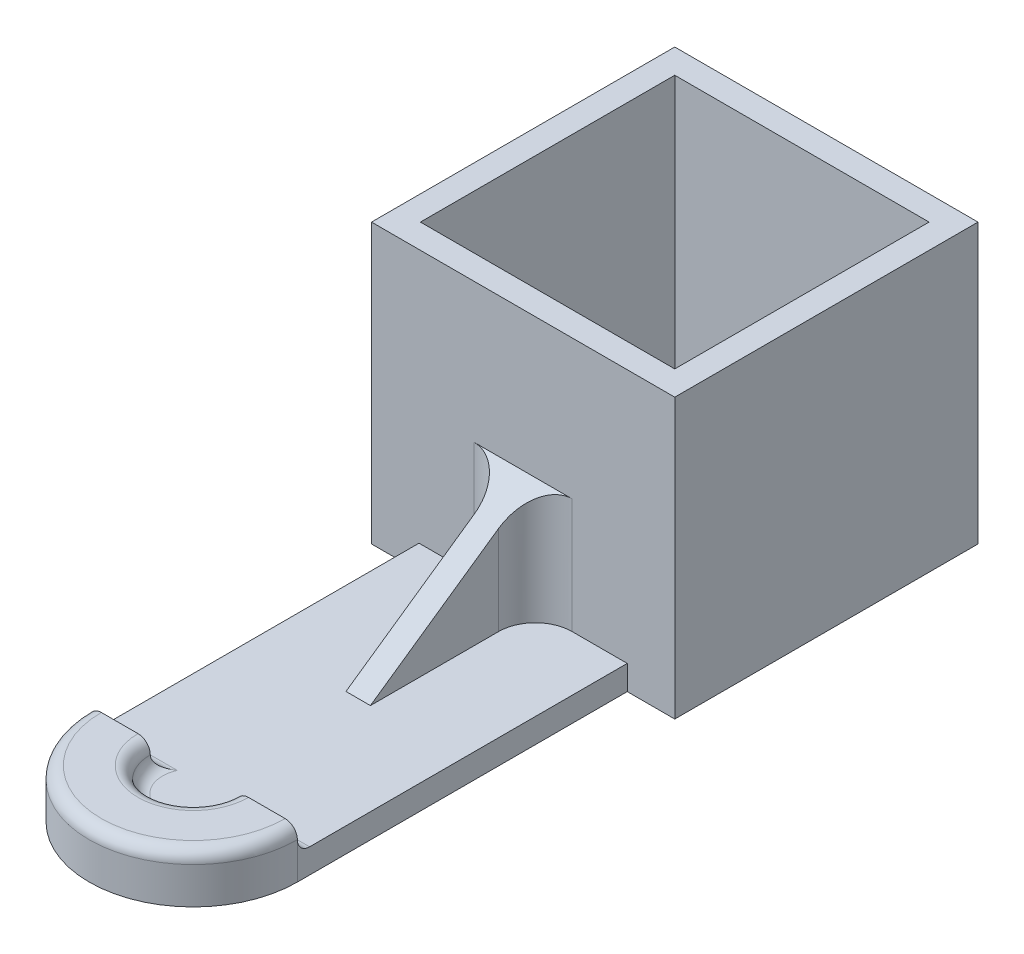
SolidWorks part; units mm, degrees
ref_plane "Front Plane" through (0, 0, 0) normal (0, 0, 1) x (1, 0, 0)
ref_plane "Top Plane" through (0, 0, 0) normal (0, 1, 0) x (1, 0, 0)
ref_plane "Right Plane" through (0, 0, 0) normal (1, 0, 0) x (0, 0, -1)
sketch "Sketch1" plane through (0, 0, 0) normal (0, 1, 0) x (1, 0, 0)
  line L1 (0, 0) -> (20.8008, 0)
  line L2 (0, 0) -> (0, 20.8008)
  line L3 (0, 20.8008) -> (20.8008, 20.8008)
  line L4 (20.8008, 0) -> (20.8008, 20.8008)
  dimension "D1" = 20.8008
extrude "Extrude-Thin1" add sketch "Sketch1" along normal blind 20.8008 thin thin type one direction wall 2
sketch "Sketch2" plane through (0, 0, 0) normal (0, -1, 0) x (1, 0, 0)
  line L4 (-2, 2) -> (-2, -22.8008)
  line L5 (-2, -22.8008) -> (22.8008, -22.8008)
  line L6 (22.8008, -22.8008) -> (22.8008, 2)
  line L7 (22.8008, 2) -> (-2, 2)
  line L8 (-2, 2) -> (-2, -22.8008)
  line L9 (-2, -22.8008) -> (22.8008, -22.8008)
  line L10 (22.8008, -22.8008) -> (22.8008, 2)
  line L11 (22.8008, 2) -> (-2, 2)
  dimension "D1" = 0
extrude "Boss-Extrude1" add sketch "Sketch2" along normal blind 2
sketch "Sketch4" plane through (0, -2, 0) normal (0, -1, 0) x (1, 0, 0)
  line L0 (10.4004, 2) -> (10.4004, 28.9804) construction
  line L1 (22.8008, 2) -> (-2, 2) construction
  line L2 (1.885, 2) -> (1.885, 28.9804)
  line L3 (18.9159, 2) -> (18.9159, 28.9804)
  arc A0 (1.885, 2) -> (18.9159, 2) centre (10.4004, 2) ccw
  arc A1 (18.9159, 28.9804) -> (1.885, 28.9804) centre (10.4004, 28.9804) ccw
  point P4 (10.4004, 15.4902)
  point P9 (10.4004, 48.3186)
  point P10 (10.4004, 28.9804)
extrude "Boss-Extrude2" add sketch "Sketch4" against normal blind 2
ref_plane "Plane1" through (10.4004, 0, 0) normal (1, 0, 0) x (0, 0, -1)
sketch "Sketch5" plane through (10.4004, 0, 0) normal (1, 0, 0) x (0, 0, -1)
  line L0 (-2, 9.4004) -> (-15.4902, 0)
  line L1 (-2, 20.8008) -> (-2, -2) construction
  line L2 (-2, 0) -> (-28.9804, 0) construction
  line L3 (-2, 9.4004) -> (-2, 0)
  line L4 (-2, 0) -> (-15.4902, 0)
extrude "Boss-Extrude3" add sketch "Sketch5" along normal mid plane 2
fillet "Fillet2" radius 3 2 edges at (11.4004, 4.7002, 2) (9.4004, 4.7002, 2)
sketch "Sketch6" plane through (0, 0, 0) normal (0, 1, 0) x (1, 0, 0)
  arc A0 (1.885, -28.9804) -> (18.9159, -28.9804) centre (10.4004, -28.9804) ccw construction
  arc A1 (1.885, -28.9804) -> (18.9159, -28.9804) centre (10.4004, -28.9804) ccw
extrude "Extrude-Thin2" add sketch "Sketch6" along normal blind 2 thin thin type one direction reverse wall 5
fillet "Fillet3" radius 1 5 edges at (16.4159, 0, 28.9804) (4.385, 0, 28.9804) (10.4004, 2, 37.4959) (10.4004, 2, 32.4959) (10.4004, 0, 32.4959)
